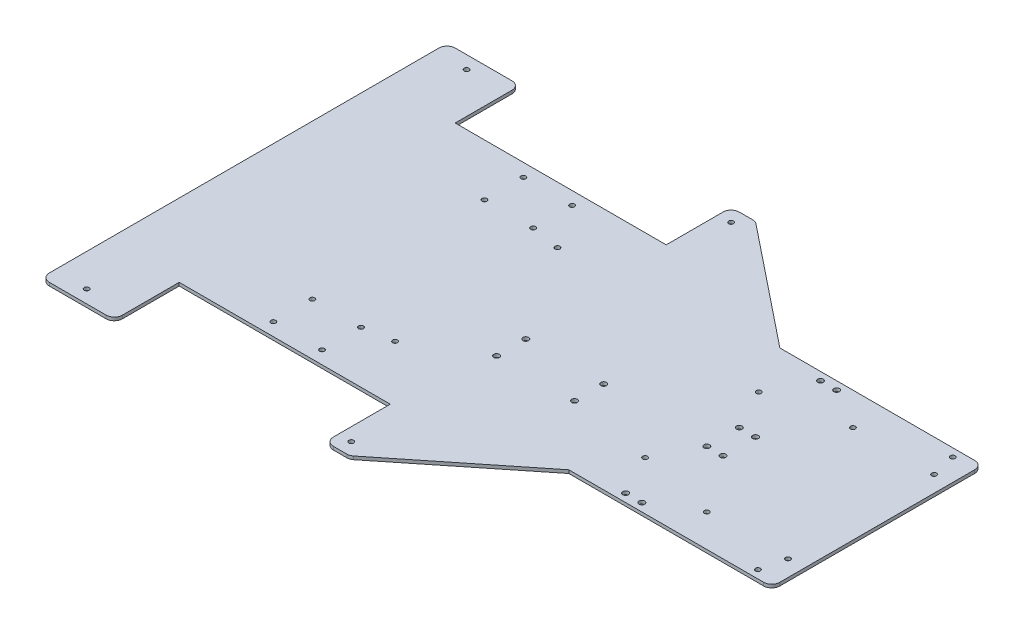
SolidWorks part; units mm, degrees
ref_plane "정면" through (0, 0, 0) normal (0, 0, 1) x (1, 0, 0)
ref_plane "윗면" through (0, 0, 0) normal (0, 1, 0) x (1, 0, 0)
ref_plane "우측면" through (0, 0, 0) normal (1, 0, 0) x (0, 0, -1)
sketch "스케치1" plane through (0, 0, 0) normal (0, 1, 0) x (1, 0, 0)
  line L1 (-195, -125) -> (195, -125)
  line L2 (-195, -125) -> (-195, 125)
  line L3 (-195, 125) -> (195, 125)
  line L4 (195, -125) -> (195, 125)
  line L5 (-195, -125) -> (195, 125) construction
  line L6 (-195, 125) -> (195, -125) construction
  point P0 (0, 0)
  dimension "D1" = 390
  dimension "D2" = 250
extrude "보스-돌출1" add sketch "스케치1" along normal blind 2
sketch "스케치2" plane through (0, 2, 0) normal (0, 1, 0) x (1, 0, 0)
  line L5 (195, 125) -> (-195, 125) construction
  line L6 (-150, 125) -> (-20, 125)
  line L7 (-150, 125) -> (-150, 85)
  line L8 (-150, 85) -> (-20, 85)
  line L9 (-20, 125) -> (-20, 85)
  line L10 (-150, -125) -> (-20, -125)
  line L11 (-150, -125) -> (-150, -85)
  line L12 (-150, -85) -> (-20, -85)
  line L13 (-20, -125) -> (-20, -85)
  line L14 (-195, -125) -> (195, -125) construction
  line L15 (70, 125) -> (195, 125)
  line L16 (70, 125) -> (70, 65)
  line L17 (70, 65) -> (195, 65)
  line L18 (195, 125) -> (195, 65)
  line L19 (70, -125) -> (195, -125)
  line L20 (70, -125) -> (70, -65)
  line L21 (70, -65) -> (195, -65)
  line L22 (195, -125) -> (195, -65)
  line L23 (195, -125) -> (195, 125) construction
  line L24 (-195, 125) -> (-195, -125) construction
  dimension "D1" = 130
  dimension "D2" = 40
  dimension "D3" = 40
  dimension "D4" = 60
  dimension "D5" = 60
  dimension "D6" = 45
  dimension "D7" = 125
extrude "컷-돌출1" cut sketch "스케치2" against normal blind 5
sketch "스케치3" plane through (0, 2, 0) normal (0, 1, 0) x (1, 0, 0)
  line L0 (-5, 125) -> (70, 65)
  line L2 (70, -65) -> (-5, -125)
  line L4 (-5, 125) -> (70, 125)
  line L5 (-5, -125) -> (70, -125)
  line L6 (70, -65) -> (70, -125)
  line L7 (70, 65) -> (70, 125)
  dimension "D1" = 75
  dimension "D2" = 75
extrude "컷-돌출2" cut sketch "스케치3" against normal blind 10
fillet "필렛1" radius 5 10 edges at (-20, 1, 125) (-20, 1, -125) (-5, 1, 125) (-5, 1, -125) (195, 1, -65) (195, 1, 65) (-195, 1, -125) (-195, 1, 125) (-150, 1, -125) (-150, 1, 125)
sketch "스케치4" plane through (0, 2, 0) normal (0, 1, 0) x (1, 0, 0)
  line L0 (-195, 0) -> (195, 0) construction
  line L1 (-100, 77) -> (-70, 77) construction
  line L2 (-100, 77) -> (-100, 53) construction
  line L3 (-100, 53) -> (-70, 53) construction
  line L4 (-70, 77) -> (-70, 53) construction
  line L5 (-100, 77) -> (-70, 53) construction
  line L6 (-100, 53) -> (-70, 77) construction
  line L7 (-195, 120) -> (-195, -120) construction
  line L8 (195, -60) -> (195, 60) construction
  line L9 (-150, 85) -> (-20, 85) construction
  line L10 (-100, -53) -> (-70, -77) construction
  line L11 (-100, -77) -> (-70, -53) construction
  line L12 (-70, -77) -> (-70, -53) construction
  line L13 (-100, -53) -> (-70, -53) construction
  line L14 (-100, -77) -> (-100, -53) construction
  line L15 (-100, -77) -> (-70, -77) construction
  line L17 (100, -60) -> (110, -60) construction
  line L18 (100, -60) -> (100, 60) construction
  line L19 (100, 60) -> (110, 60) construction
  line L20 (110, -60) -> (110, 60) construction
  line L21 (100, -60) -> (110, 60) construction
  line L22 (100, 60) -> (110, -60) construction
  line L23 (100, -10) -> (110, -10) construction
  line L24 (100, -10) -> (100, 10) construction
  line L25 (100, 10) -> (110, 10) construction
  line L26 (110, -10) -> (110, 10) construction
  line L27 (100, -10) -> (110, 10) construction
  line L28 (100, 10) -> (110, -10) construction
  circle A0 centre (-100, 77) radius 1.5
  circle A1 centre (-70, 77) radius 1.5
  circle A2 centre (-70, 53) radius 1.5
  circle A3 centre (-100, 53) radius 1.5
  circle A4 centre (-100, -53) radius 1.5
  circle A5 centre (-70, -53) radius 1.5
  circle A6 centre (-70, -77) radius 1.5
  circle A7 centre (-100, -77) radius 1.5
  circle A8 centre (100, 60) radius 1.75
  circle A9 centre (110, 60) radius 1.75
  circle A10 centre (100, 10) radius 1.75
  circle A11 centre (110, 10) radius 1.75
  circle A12 centre (100, -10) radius 1.75
  circle A13 centre (110, -10) radius 1.75
  circle A14 centre (100, -60) radius 1.75
  circle A15 centre (110, -60) radius 1.75
  point P0 (-85, 65)
  point P25 (-85, -65)
  point P26 (105, 0)
  point P31 (105, 0)
  dimension "D5" = 3
  dimension "D9" = 3.5
  dimension "D1" = 30
  dimension "D2" = 24
  dimension "D3" = 95
  dimension "D4" = 32
  dimension "D6" = 120
  dimension "D7" = 10
  dimension "D8" = 20
  dimension "D10" = 85
extrude "컷-돌출3" cut sketch "스케치4" against normal through all
sketch "스케치5" plane through (0, 2, 0) normal (0, 1, 0) x (1, 0, 0)
  line L0 (-20, -85) -> (-150, -85) construction
  line L1 (-13, -26.5) -> (35, -26.5) construction
  line L2 (-13, -26.5) -> (-13, -8.5) construction
  line L3 (-13, -8.5) -> (35, -8.5) construction
  line L4 (35, -26.5) -> (35, -8.5) construction
  line L5 (195, -60) -> (195, 60) construction
  circle A1 centre (-13, -8.5) radius 1.75
  circle A2 centre (35, -8.5) radius 1.75
  circle A3 centre (-13, -26.5) radius 1.75
  circle A4 centre (35, -26.5) radius 1.75
  dimension "D1" = 3.5
  dimension "D2" = 58.5
  dimension "D3" = 18
  dimension "D4" = 48
  dimension "D5" = 160
extrude "컷-돌출4" cut sketch "스케치5" against normal through all
sketch "스케치6" plane through (0, 2, 0) normal (0, 1, 0) x (1, 0, 0)
  line L0 (70, 65) -> (190, 65) construction
  line L1 (135, 45) -> (185, 45) construction
  line L2 (135, 45) -> (135, -45) construction
  line L3 (135, -45) -> (185, -45) construction
  line L4 (185, 45) -> (185, -45) construction
  line L5 (190, -65) -> (70, -65) construction
  line L6 (195, -60) -> (195, 60) construction
  circle A0 centre (135, 45) radius 1.5
  circle A1 centre (185, 45) radius 1.5
  circle A2 centre (135, -45) radius 1.5
  circle A3 centre (185, -45) radius 1.5
  dimension "D5" = 3
  dimension "D1" = 20
  dimension "D2" = 20
  dimension "D3" = 10
  dimension "D4" = 50
extrude "컷-돌출5" cut sketch "스케치6" against normal through all
sketch "스케치7" plane through (0, 2, 0) normal (0, 1, 0) x (1, 0, 0)
  line L0 (-6.7539, 125) -> (-15, 125) construction
  line L1 (-175, 117) -> (-12, 117) construction
  line L2 (-175, 117) -> (-175, -117) construction
  line L3 (-175, -117) -> (-12, -117) construction
  line L4 (-12, 117) -> (-12, -117) construction
  line L5 (-20, 85) -> (-20, 120) construction
  line L6 (-15, -125) -> (-6.7539, -125) construction
  line L7 (-52, 50) -> (-52, -50) construction
  line L8 (-195, 120) -> (-195, -120) construction
  line L9 (181.5, 60) -> (181.5, -60) construction
  line L10 (195, -60) -> (195, 60) construction
  line L11 (190, -65) -> (70, -65) construction
  line L12 (70, 65) -> (190, 65) construction
  line L13 (87, 35) -> (87, -35) construction
  line L14 (-150, 85) -> (-20, 85) construction
  line L15 (-20, -85) -> (-150, -85) construction
  circle A0 centre (-12, 117) radius 1.5
  circle A1 centre (-12, -117) radius 1.5
  circle A2 centre (181.5, 60) radius 1.5
  circle A3 centre (181.5, -60) radius 1.5
  circle A4 centre (-175, 117) radius 1.5
  circle A5 centre (-175, -117) radius 1.5
  circle A6 centre (87, 35) radius 1.5
  circle A7 centre (87, -35) radius 1.5
  circle A9 centre (-52, 50) radius 1.5
  circle A10 centre (-52, -50) radius 1.5
  dimension "D1" = 8
  dimension "D2" = 8
  dimension "D3" = 8
  dimension "D4" = 20
  dimension "D5" = 3
  dimension "D7" = 5
  dimension "D8" = 5
  dimension "D10" = 30
  dimension "D11" = 108
  dimension "D13" = 35
  dimension "D14" = 35
  dimension "D6" = 13.5
  dimension "D9" = 70
  dimension "D12" = 40
extrude "컷-돌출6" cut sketch "스케치7" against normal through all
